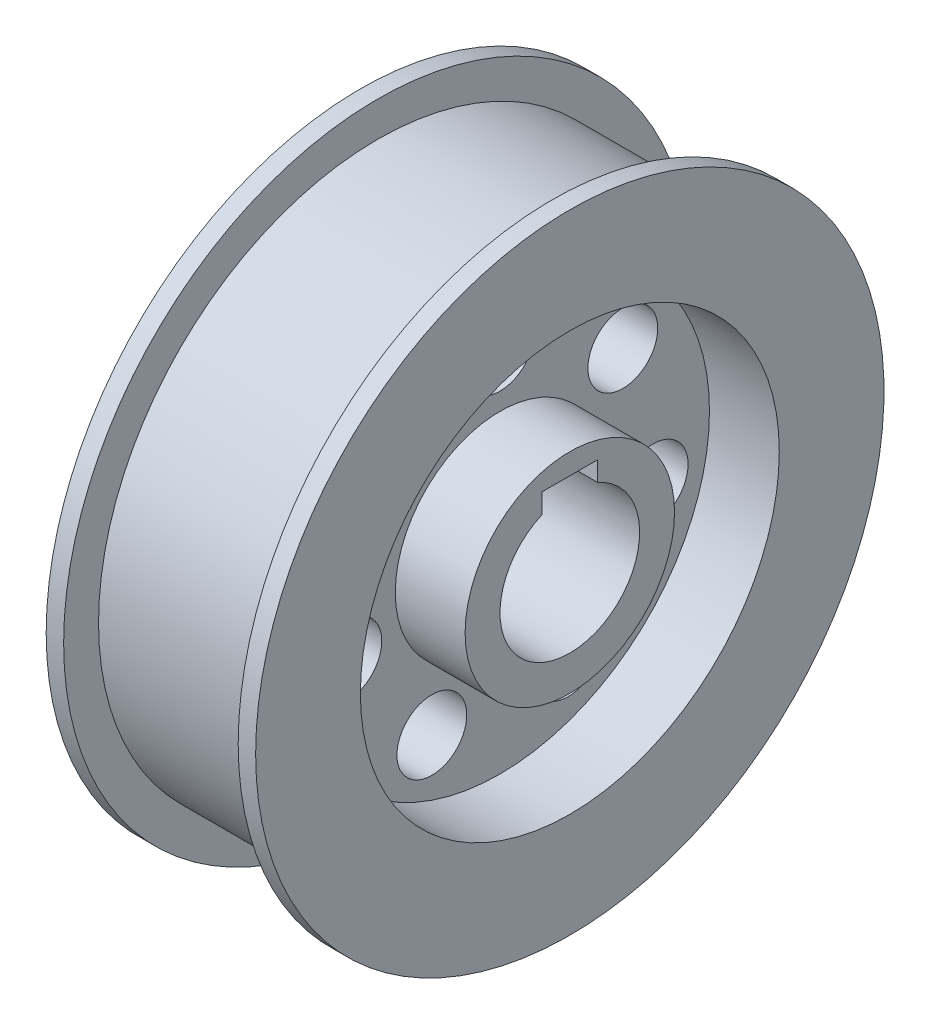
SolidWorks part; units mm, degrees
material "Plain Carbon Steel"
ref_plane "Front Plane" through (0, 0, 0) normal (0, 0, 1) x (1, 0, 0)
ref_plane "Top Plane" through (0, 0, 0) normal (0, 1, 0) x (1, 0, 0)
ref_plane "Right Plane" through (0, 0, 0) normal (1, 0, 0) x (0, 0, -1)
sketch "Sketch1" plane through (0, 0, 0) normal (1, 0, 0) x (0, 0, -1)
  line L2 (-4, 9.1652) -> (-4, 12)
  line L3 (-4, 12) -> (4, 12)
  line L4 (4, 9.1652) -> (4, 12)
  circle A0 centre (0, 0) radius 15
  circle A1 centre (0, 0) radius 30 construction
  circle A2 centre (0, 0) radius 40 construction
  arc A3 (-4, 9.1652) -> (4, 9.1652) centre (0, 0) ccw
  point P10 (0, 12)
  dimension "D1" = 30
  dimension "D2" = 60
  dimension "D3" = 80
  dimension "D4" = 20
  dimension "D5" = 8
  dimension "D6" = 12
extrude "Boss-Extrude1" add sketch "Sketch1" along normal blind 15 and the other way blind 15
sketch "Sketch2" plane through (-15, 0, 0) normal (-1, 0, 0) x (0, 0, 1)
  circle A0 centre (0, 0) radius 13
  circle A1 centre (0, 0) radius 3.5
  dimension "D1" = 26
  dimension "D2" = 7
extrude "Boss-Extrude2" add sketch "Sketch2" against normal blind 5
sketch "Sketch3" plane through (0, 0, 0) normal (1, 0, 0) x (0, 0, -1)
  circle A0 centre (0, 0) radius 30
  circle A2 centre (0, 22.5) radius 5
  circle A3 centre (17.5912, 14.0285) radius 5
  circle A4 centre (21.9359, -5.0067) radius 5
  circle A5 centre (9.7624, -20.2718) radius 5
  circle A6 centre (-9.7624, -20.2718) radius 5
  circle A7 centre (-21.9359, -5.0067) radius 5
  circle A8 centre (-17.5912, 14.0285) radius 5
  circle A9 centre (0, 0) radius 13.5
  point P19 (0, 0)
  dimension "D1" = 60
  dimension "D2" = 10
  dimension "D5" = 27
  dimension "D3" = 22.5
  dimension "D4" = 7
extrude "Boss-Extrude3" add sketch "Sketch3" along normal blind 5 and the other way blind 5
sketch "Sketch4" plane through (0, 0, 0) normal (1, 0, 0) x (0, 0, -1)
  circle A0 centre (0, 0) radius 30
  circle A1 centre (0, 0) radius 40
  dimension "D1" = 80
  dimension "D2" = 60
extrude "Boss-Extrude4" add sketch "Sketch4" along normal blind 15 and the other way blind 15
sketch "Sketch5" plane through (0, 0, 0) normal (0, 0, 1) x (1, 0, 0)
  line L0 (-15, 36) -> (-15, 45)
  line L1 (-15, 40) -> (-15, -40) construction
  line L2 (-15, 45) -> (-12.5, 45)
  line L3 (-12.5, 45) -> (-12.5, 37)
  line L4 (-12.5, 37) -> (12.5, 37)
  line L5 (12.5, 37) -> (12.5, 45)
  line L6 (12.5, 45) -> (15, 45)
  line L7 (15, 45) -> (15, 36)
  line L8 (15, -40) -> (15, 40) construction
  line L9 (15, 36) -> (-15, 36)
  line L10 (15, 40) -> (-15, 40) construction
  line L11 (0, 0) -> (31.3593, 0) construction
  dimension "D1" = 25
  dimension "D2" = 5
  dimension "D3" = 1
  dimension "D4" = 8
revolve "Revolve1" add sketch "Sketch5" angle 360 about L11
